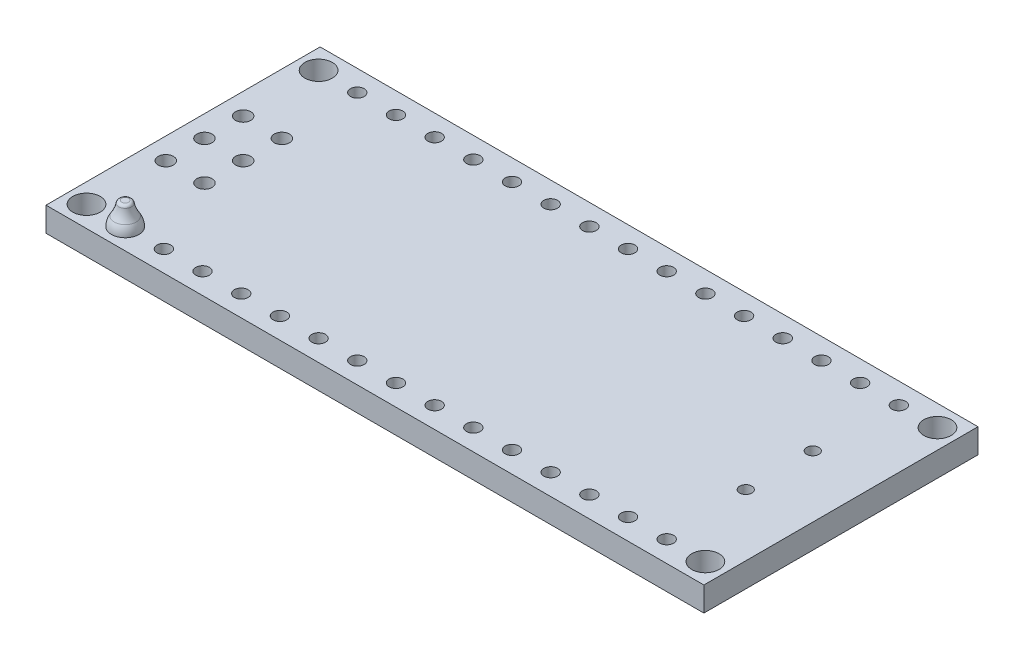
SolidWorks part; units mm, degrees
material "E-Glass Fiber"
ref_plane "Front Plane" through (0, 0, 0) normal (0, 0, 1) x (1, 0, 0)
ref_plane "Top Plane" through (0, 0, 0) normal (0, 1, 0) x (1, 0, 0)
ref_plane "Right Plane" through (0, 0, 0) normal (1, 0, 0) x (0, 0, -1)
sketch "Sketch1" plane through (0, 0, 0) normal (0, 1, 0) x (1, 0, 0)
  line L0 (0, 7.62) -> (-3.82, 7.62) construction
  line L1 (-3.82, 16.62) -> (39.38, 16.62)
  line L2 (-3.82, 16.62) -> (-3.82, -1.38)
  line L3 (-3.82, -1.38) -> (39.38, -1.38)
  line L4 (39.38, 16.62) -> (39.38, -1.38)
  line L5 (0, 0) -> (35.56, 0) construction
  line L6 (0, 0) -> (0, 15.24) construction
  line L7 (0, 15.24) -> (35.56, 15.24) construction
  line L8 (35.56, 0) -> (35.56, 15.24) construction
  line L10 (35.56, 7.62) -> (39.38, 7.62) construction
  dimension "D1" = 43.2
  dimension "D2" = 18
  dimension "D3" = 15.24
  dimension "D4" = 35.56
extrude "Boss-Extrude2" add sketch "Sketch1" along normal blind 1.6
sketch "Sketch2" plane through (0, 0, 0) normal (0, 1, 0) x (1, 0, 0)
  line L0 (0, -0.88) -> (0, 0.88) construction
  line L2 (-0.88, 0) -> (0.88, 0) construction
  circle A0 centre (0, 0) radius 0.45
  circle A1 centre (0, 15.24) radius 0.45
  dimension "D1" = 0.9
  dimension "D2" = 15.24
extrude "Cut-Extrude2" cut sketch "Sketch2" along normal blind 1.6
pattern_linear "LPattern1" count 15 spacing 2.54 along (1, 0, 0) of "Cut-Extrude2"
sketch "Sketch3" plane through (0, 0, 0) normal (0, 1, 0) x (1, 0, 0)
  line L1 (-0.88, 0) -> (0.88, 0) construction
  line L2 (0, -0.88) -> (0, 0.88) construction
  circle A0 centre (0.127, 10.16) radius 0.5
  circle A1 centre (-2.413, 10.16) radius 0.5
  circle A2 centre (-2.413, 7.62) radius 0.5
  circle A3 centre (-2.413, 5.08) radius 0.5
  circle A4 centre (0.127, 5.08) radius 0.5
  circle A5 centre (0.127, 7.62) radius 0.5
  dimension "D1" = 1
  dimension "D5" = 7.62
  dimension "D2" = 2.54
  dimension "D3" = 2.54
  dimension "D4" = 2.54
  dimension "D6" = 2.54
  dimension "D7" = 0.127
extrude "Cut-Extrude4" cut sketch "Sketch3" along normal blind 1.6
sketch "Sketch4" plane through (0, 0, 0) normal (0, 1, 0) x (1, 0, 0)
  line L0 (-0.88, 0) -> (0.88, 0) construction
  line L1 (0, -0.88) -> (0, 0.88) construction
  circle A0 centre (38.1, 15.24) radius 0.9
  circle A1 centre (38.1, 0) radius 0.9
  circle A2 centre (-2.54, 0) radius 0.9
  circle A3 centre (-2.54, 15.24) radius 0.9
  dimension "D3" = 1.8
  dimension "D1" = 40.64
  dimension "D2" = 2.54
  dimension "D4" = 15.24
  dimension "D5" = 15.24
extrude "Cut-Extrude5" cut sketch "Sketch4" along normal blind 1.6
sketch "Sketch5" plane through (0, 1.6, 0) normal (0, 1, 0) x (1, 0, 0)
  circle A0 centre (38.1, 15.24) radius 0.9
  circle A1 centre (38.1, 15.24) radius 1.275
  circle A2 centre (38.1, 15.24) radius 0.9 construction
  circle A3 centre (38.1, 0) radius 0.9
  circle A4 centre (38.1, 0) radius 0.9 construction
  circle A5 centre (38.1, 0) radius 1.275
  circle A6 centre (-2.54, 15.24) radius 0.9
  circle A7 centre (-2.54, 15.24) radius 1.275
  circle A8 centre (-2.54, 0) radius 0.9
  circle A9 centre (-2.54, 0) radius 1.275
  circle A10 centre (-2.54, 15.24) radius 0.9 construction
  circle A11 centre (-2.54, 0) radius 0.9 construction
  dimension "D1" = 2.55
extrude "Boss-Extrude3" [suppressed] add sketch "Sketch5" along normal blind 0.1
sketch "Sketch6" plane through (0, 0, 0) normal (1, 0, 0) x (0, 0, -1)
  line L0 (0, 1.6) -> (0.9, 1.6)
  line L1 (-1.38, 1.6) -> (16.62, 1.6) construction
  line L2 (0.2252, 3.1) -> (0, 3.1)
  line L3 (0, 2.53) -> (0, -2.53) construction
  line L4 (0, 3.1) -> (0, 1.6)
  line L5 (0, 1.3722) -> (0, 3.4408) construction
  arc A0 (0.9, 1.6) -> (0.7139, 2.2122) centre (-0.2, 1.6) ccw
  arc A1 (0.7139, 2.2122) -> (0.4221, 2.9352) centre (2.2924, 3.2697) cw
  arc A2 (0.4221, 2.9352) -> (0.2252, 3.1) centre (0.2252, 2.9) ccw
  point P16 (0.4, 3.1)
  dimension "D4" = 1.1
  dimension "D5" = 1.9
  dimension "D6" = 0.2
  dimension "D1" = 1.5
  dimension "D2" = 0.8
  dimension "D3" = 1.8
revolve "Revolve1" add sketch "Sketch6" angle 360 about L5
pattern_linear "LPattern2" [suppressed] count 2 spacing 15.24 count 15 spacing 2.54 of bodies 108
ref_plane "Plane3" through (0, 0, -5.08) normal (0, 0, 1) x (1, 0, 0)
sketch "Sketch7" plane through (0, 0, -5.08) normal (0, 0, 1) x (1, 0, 0)
  line L0 (0.127, 3.889) -> (0.127, -2.5597) construction
  line L2 (0, -1.705) -> (0, 1.705) construction
  line L3 (0.127, 0) -> (1.027, 0)
  line L4 (9.9, 0) -> (-9.9, 0) construction
  line L5 (0.127, 0) -> (0.127, -1.5)
  line L6 (0.127, -1.5) -> (0.3395, -1.5)
  arc A0 (0.538, -1.325) -> (0.807, -0.66) centre (1.927, -1.5) cw
  arc A1 (0.807, -0.66) -> (1.027, 0) centre (-0.073, 0) ccw
  arc A2 (0.3395, -1.5) -> (0.538, -1.325) centre (0.3395, -1.3) ccw
  point P16 (0.527, -1.5)
  dimension "D5" = 1.1
  dimension "D6" = 0.2
  dimension "D1" = 0.127
  dimension "D2" = 1.5
  dimension "D3" = 0.8
  dimension "D4" = 1.8
revolve "Revolve2" add sketch "Sketch7" angle 360 about L0
pattern_linear "LPattern3" count 2 spacing 2.54 along (-1, 0, 0) count 3 spacing 2.54 along (0, 0, -1) of "Revolve2"
sketch "Sketch8" plane through (0, 0, 0) normal (0, -1, 0) x (1, 0, 0)
  circle A0 centre (38.1, 0) radius 0.9
  circle A1 centre (38.1, 0) radius 1.275
  circle A2 centre (38.1, -15.24) radius 1.275
  circle A3 centre (38.1, -15.24) radius 0.9
  circle A4 centre (38.1, -15.24) radius 0.9 construction
  circle A5 centre (38.1, 0) radius 0.9 construction
  circle A6 centre (-2.54, 0) radius 0.9
  circle A7 centre (-2.54, 0) radius 1.275
  circle A8 centre (-2.54, -15.24) radius 0.9
  circle A9 centre (-2.54, -15.24) radius 1.275
  circle A10 centre (-2.54, 0) radius 0.9 construction
  circle A11 centre (-2.54, -15.24) radius 0.9 construction
  dimension "D1" = 2.55
extrude "Boss-Extrude4" [suppressed] add sketch "Sketch8" along normal blind 0.1
sketch "Sketch9" plane through (0, 0, 0) normal (0, 1, 0) x (1, 0, 0)
  line L0 (-2.53, 0) -> (2.53, 0) construction
  line L1 (39.38, -1.38) -> (39.38, 16.62) construction
  circle A0 centre (35.33, 5.42) radius 0.4
  circle A1 centre (35.33, 9.82) radius 0.4
  dimension "D1" = 0.8
  dimension "D2" = 4.4
  dimension "D3" = 5.42
  dimension "D4" = 4.05
extrude "Cut-Extrude6" cut sketch "Sketch9" along normal blind 10
